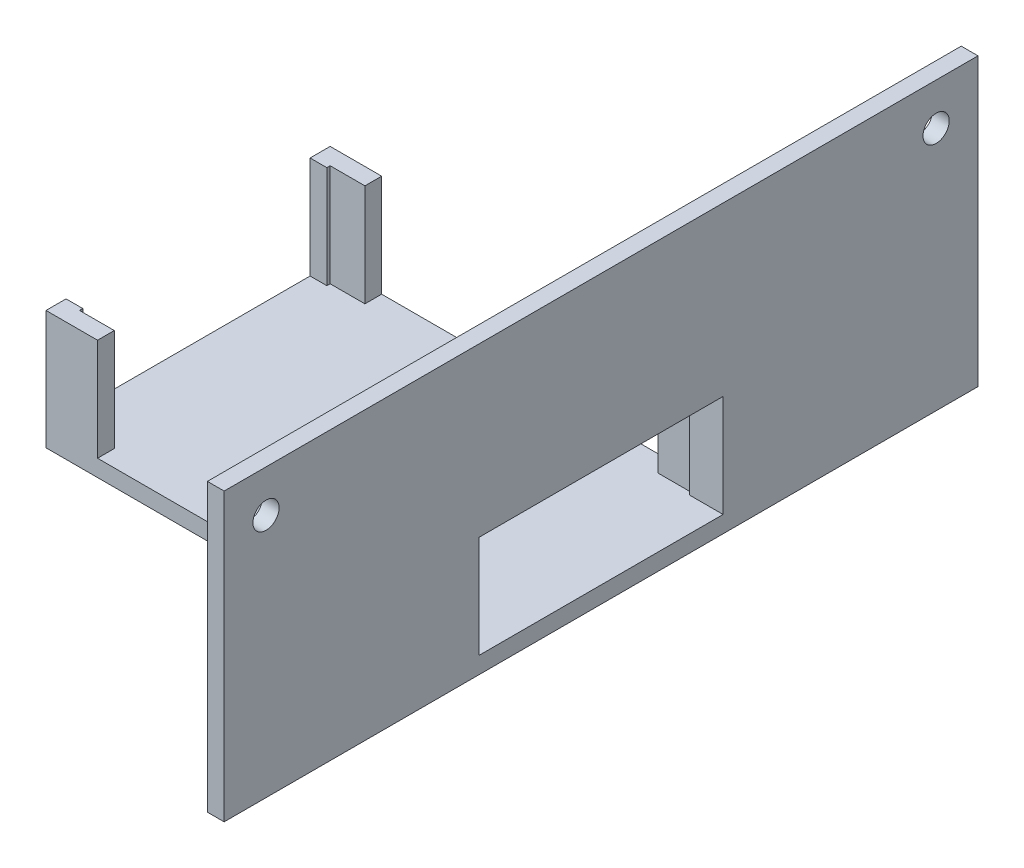
SolidWorks part; units mm, degrees
material "ABS"
ref_plane "Front Plane" through (0, 0, 0) normal (0, 0, 1) x (1, 0, 0)
ref_plane "Top Plane" through (0, 0, 0) normal (0, 1, 0) x (1, 0, 0)
ref_plane "Right Plane" through (0, 0, 0) normal (1, 0, 0) x (0, 0, -1)
sketch "Sketch1" plane through (0, 0, 0) normal (0, 1, 0) x (1, 0, 0)
  line L1 (-30.04, 43.08) -> (30.04, 43.08)
  line L2 (-30.04, 43.08) -> (-30.04, 0)
  line L3 (-30.04, 0) -> (30.04, 0)
  line L4 (30.04, 43.08) -> (30.04, 0)
  dimension "D1" = 60.08
  dimension "D2" = 43.08
extrude "Boss-Extrude1" add sketch "Sketch1" along normal blind 18.04
shell "Shell1" thickness 2.54 removed face at (0, 18.04, -21.54)
sketch "Sketch2" plane through (30.04, 0, 0) normal (1, 0, 0) x (0, 0, -1)
  line L0 (0, 0) -> (43.08, 0) construction
  line L1 (78.69, 0) -> (-35.61, 0)
  line L2 (78.69, 0) -> (78.69, 43.44)
  line L3 (78.69, 43.44) -> (-35.61, 43.44)
  line L4 (-35.61, 0) -> (-35.61, 43.44)
  line L6 (0, 18.04) -> (43.08, 18.04) construction
  point P7 (21.54, 0)
  point P8 (21.54, 0)
  dimension "D1" = 25.4
  dimension "D2" = 114.3
extrude "Boss-Extrude2" add sketch "Sketch2" along normal blind 2.54
fillet "Fillet1" radius 5.08 1 edges at (30.04, 18.04, -21.54)
sketch "Sketch3" plane through (30.04, 0, 0) normal (-1, 0, 0) x (0, 0, 1)
  line L0 (-78.69, 0) -> (-78.69, 43.44) construction
  line L1 (-78.69, 43.44) -> (35.61, 43.44) construction
  line L2 (35.61, 43.44) -> (35.61, 0) construction
  circle A0 centre (-72.34, 37.09) radius 1.9844
  circle A1 centre (29.26, 37.09) radius 1.9844
  dimension "D1" = 3.9688
  dimension "D2" = 6.35
  dimension "D3" = 6.35
  dimension "D4" = 6.35
  dimension "D5" = 6.35
extrude "Cut-Extrude1" cut sketch "Sketch3" against normal through all both and the other way through all
sketch "Sketch5" plane through (0, 0, 0) normal (0, 0, 1) x (1, 0, 0)
  line L0 (0, -23.892) -> (0, 23.892) construction
  line L1 (22.225, 2.54) -> (-22.225, 2.54)
  line L2 (22.225, 2.54) -> (22.225, 18.04)
  line L3 (22.225, 18.04) -> (-22.225, 18.04)
  line L4 (-22.225, 2.54) -> (-22.225, 18.04)
  line L5 (22.225, 2.54) -> (-22.225, 18.04) construction
  line L6 (22.225, 18.04) -> (-22.225, 2.54) construction
  line L11 (-30.04, 18.04) -> (24.96, 18.04) construction
  line L12 (-27.5, 2.54) -> (27.5, 2.54) construction
  point P0 (0, 10.29)
  dimension "D1" = 44.45
extrude "Cut-Extrude2" cut sketch "Sketch5" against normal through all
sketch "Sketch6" plane through (-30.04, 0, 0) normal (-1, 0, 0) x (0, 0, 1)
  line L0 (-43.08, 18.04) -> (0, 18.04) construction
  line L1 (-3.04, 2.54) -> (-40.04, 2.54)
  line L2 (-3.04, 2.54) -> (-3.04, 18.04)
  line L3 (-3.04, 18.04) -> (-40.04, 18.04)
  line L4 (-40.04, 2.54) -> (-40.04, 18.04)
  line L5 (-3.04, 2.54) -> (-40.04, 18.04) construction
  line L6 (-3.04, 18.04) -> (-40.04, 2.54) construction
  line L7 (-40.54, 2.54) -> (-2.54, 2.54) construction
  line L8 (-21.54, 0) -> (-21.54, 18.04) construction
  line L9 (-43.08, 0) -> (0, 0) construction
  point P0 (-21.54, 10.29)
  point P13 (0, 0)
  dimension "D1" = 37
extrude "Cut-Extrude3" cut sketch "Sketch6" against normal through all
